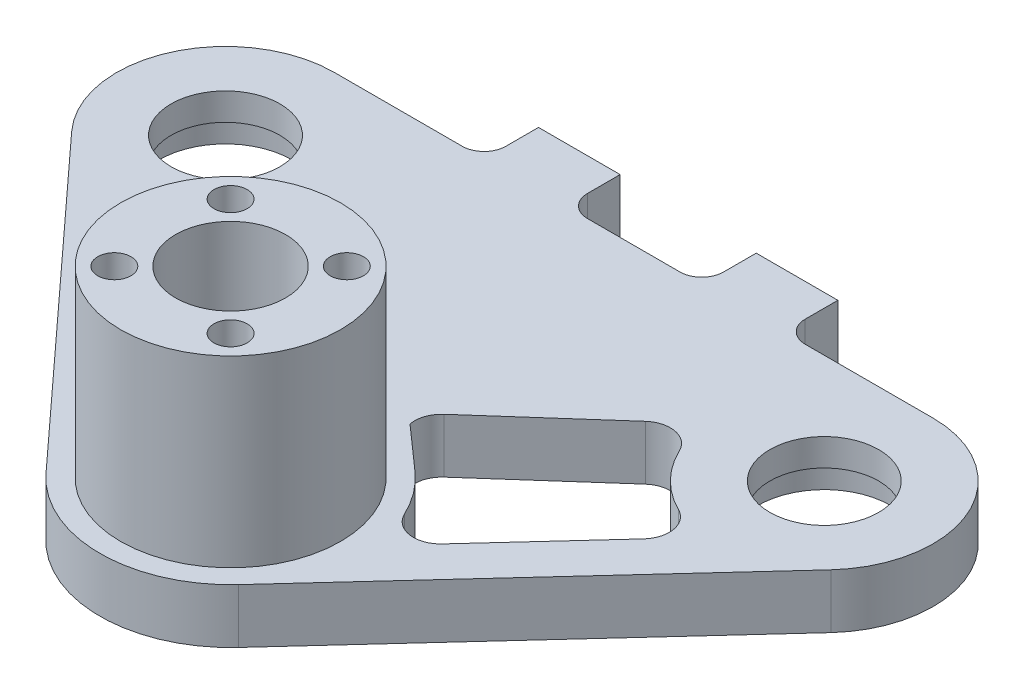
SolidWorks part; units mm, degrees
material "PLA Infill"
ref_plane "Front Plane" through (0, 0, 0) normal (0, 0, 1) x (1, 0, 0)
ref_plane "Top Plane" through (0, 0, 0) normal (0, 1, 0) x (1, 0, 0)
ref_plane "Right Plane" through (0, 0, 0) normal (1, 0, 0) x (0, 0, -1)
sketch "Sketch1" plane through (0, 0, 0) normal (0, 1, 0) x (1, 0, 0)
  line L0 (0, 0) -> (55, 54.0672) construction
  line L1 (55, 54.0672) -> (-55, 54.0672) construction
  line L2 (-55, 54.0672) -> (0, 0) construction
  line L3 (-69.7415, 40.551) -> (-17.6898, -16.2194)
  line L4 (-41.7379, 69.0378) -> (15.9145, 17.9646)
  line L5 (-47.6255, 28.2677) -> (-29.9271, 8.9649)
  line L6 (-29.0781, 47.135) -> (-9.4754, 29.7694)
  circle A0 centre (0, 0) radius 10.1
  circle A1 centre (-55, 54.0672) radius 10
  circle A2 centre (0, 0) radius 24 construction
  circle A3 centre (-55, 54.0672) radius 20 construction
  arc A4 (-69.7415, 40.551) -> (-41.7379, 69.0378) centre (-55, 54.0672) cw
  arc A5 (-17.6898, -16.2194) -> (15.9145, 17.9646) centre (0, 0) ccw
  arc A6 (-46.1521, 36.1308) -> (-36.9149, 45.5274) centre (-55, 54.0672) ccw
  arc A7 (-21.7173, 10.2157) -> (-10.5856, 21.5394) centre (0, 0) cw
  arc A8 (-29.9271, 8.9649) -> (-21.7173, 10.2157) centre (-26.2417, 12.3439) ccw
  arc A9 (-9.4754, 29.7694) -> (-10.5856, 21.5394) centre (-12.7909, 26.0268) cw
  arc A10 (-29.0781, 47.135) -> (-36.9149, 45.5274) centre (-32.3936, 43.3924) ccw
  arc A11 (-47.6255, 28.2677) -> (-46.1521, 36.1308) centre (-43.9401, 31.6467) cw
  point P22 (-23.8825, 2.3723)
  point P25 (-2.7804, 23.8384)
  point P28 (-35.0663, 52.4399)
  point P31 (-53.032, 34.1643)
  dimension "D3" = 20.2
  dimension "D4" = 20
  dimension "D5" = 48
  dimension "D6" = 40
  dimension "D9" = 5
  dimension "D1" = 77.125
  dimension "D2" = 110
  dimension "D7" = 8
  dimension "D8" = 8
extrude "Main Body" add sketch "Sketch1" along normal blind 10
sketch "Sketch2" plane through (0, 0, 0) normal (0, -1, 0) x (1, 0, 0)
  circle A0 centre (-55, -54.0672) radius 10 construction
  circle A1 centre (-55, -54.0672) radius 10 construction
  circle A2 centre (-55, -54.0672) radius 12.2
  dimension "D1" = 24.4
extrude "Bearing Recess" cut sketch "Sketch2" against normal blind 5
sketch "Sketch3" plane through (0, 0, 0) normal (0, -1, 0) x (1, 0, 0)
  circle A0 centre (0, 0) radius 21.5
  circle A1 centre (0, 0) radius 10.1
  circle A2 centre (0, 0) radius 10.1 construction
  dimension "D1" = 43
extrude "Standoff Section" add sketch "Sketch3" along normal blind 1.5
sketch "Sketch9" plane through (0, 10, 0) normal (0, 1, 0) x (1, 0, 0)
  circle A0 centre (0, 0) radius 20.2
  circle A1 centre (0, 0) radius 10.1
  dimension "D1" = 40.4
  dimension "D2" = 20.2
extrude "Boss-Extrude1" add sketch "Sketch9" along normal blind 33.7
ref_plane "Mirror Plane" through (0, 0, 0) normal (1, 0, 0) x (0, 0, -1)
sketch "Sketch6" plane through (0, 0, 0) normal (0, 1, 0) x (1, 0, 0)
  line L0 (-55, 74.0672) -> (0, 74.0672) construction
  line L1 (0, -24.86) -> (0, 24.86) construction
  line L2 (0, 74.0672) -> (0, 32.063)
  line L3 (-41.7379, 69.0378) -> (15.9145, 17.9646) construction
  line L4 (0, 32.063) -> (-41.7379, 69.0378)
  line L5 (-20, 84.0672) -> (-20, 74.0672) construction
  line L6 (-27.5, 74.0672) -> (-12.5, 74.0672) construction
  line L7 (-27.5, 78.0672) -> (-27.5, 84.0672)
  line L8 (-27.5, 84.0672) -> (-12.5, 84.0672)
  line L9 (-12.5, 78.0672) -> (-12.5, 84.0672)
  line L10 (-55, 74.0672) -> (-31.5, 74.0672)
  line L11 (-8.5, 74.0672) -> (0, 74.0672)
  arc A0 (-41.7379, 69.0378) -> (-69.7415, 40.551) centre (-55, 54.0672) ccw construction
  arc A1 (-41.7379, 69.0378) -> (-69.7415, 40.551) centre (-55, 54.0672) ccw construction
  arc A2 (-55, 74.0672) -> (-41.7379, 69.0378) centre (-55, 54.0672) cw
  arc A3 (-8.5, 74.0672) -> (-12.5, 78.0672) centre (-8.5, 78.0672) cw
  arc A4 (-31.5, 74.0672) -> (-27.5, 78.0672) centre (-31.5, 78.0672) ccw
  dimension "D4" = 4
  dimension "D1" = 10
  dimension "D2" = 20
  dimension "D3" = 15
extrude "Extra Geometry" add sketch "Sketch6" along normal blind 10
sketch "Sketch8" plane through (0, 0, -84.0672) normal (0, 0, -1) x (-1, 0, 0)
  line L0 (20, 10) -> (20, 0) construction
  line L1 (12.5, 10) -> (27.5, 10) construction
  line L2 (12.5, 0) -> (27.5, 0) construction
  circle A0 centre (20, 5) radius 2
  point P9 (20, 5)
  dimension "D1" = 4
extrude "Cut-Extrude1" cut sketch "Sketch8" against normal blind 6
mirror "Mirror2" about plane through (0, 0, 0) normal (1, 0, 0) of bodies 109 107
sketch "Sketch4" plane through (0, -1.5, 0) normal (0, -1, 0) x (1, 0, 0)
  line L0 (0, 0) -> (50000, 0) construction
  line L1 (55, -54.0672) -> (-55, -54.0672) construction
  line L2 (-10.6773, 10.6773) -> (0, 0) construction
  circle A0 centre (-10.6773, 10.6773) radius 3.05
  circle A2 centre (10.6773, 10.6773) radius 3.05
  circle A3 centre (10.6773, -10.6773) radius 3.05
  circle A4 centre (-10.6773, -10.6773) radius 3.05
  dimension "D1" = 6.1
  dimension "D2" = 15.1
  dimension "D3" = 45
  dimension "D4" = 4
extrude "M6 Bolt holes" cut sketch "Sketch4" against normal through all
